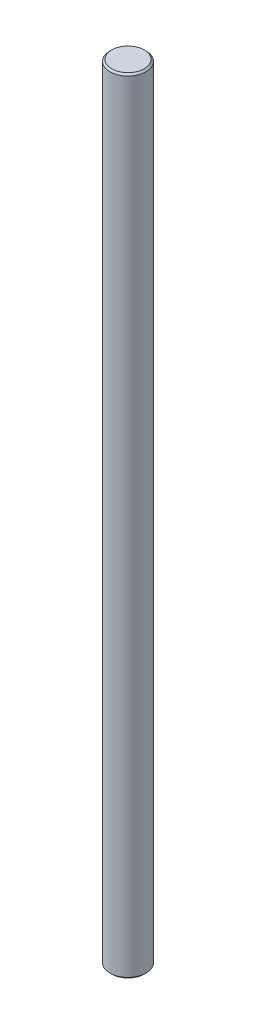
SolidWorks part; units mm, degrees
material "Acier inoxydable chromé"
ref_plane "Plan de face" through (0, 0, 0) normal (0, 0, 1) x (1, 0, 0)
ref_plane "Plan de dessus" through (0, 0, 0) normal (0, 1, 0) x (1, 0, 0)
ref_plane "Plan de droite" through (0, 0, 0) normal (1, 0, 0) x (0, 0, -1)
sketch "Esquisse1" plane through (0, 0, 0) normal (0, 1, 0) x (1, 0, 0)
  circle A0 centre (0, 0) radius 3.175
  dimension "D1" = 6.35
extrude "Boss.-Extru.1" add sketch "Esquisse1" along normal blind 138
sketch "Esquisse2" plane through (0, 0, 0) normal (0, -1, 0) x (1, 0, 0)
  circle A0 centre (0, 0) radius 3.175
chamfer "Chanfrein1" distance 0.3 angle 45 2 edges at (0, 0, 3.175) (0, 138, 3.175)
